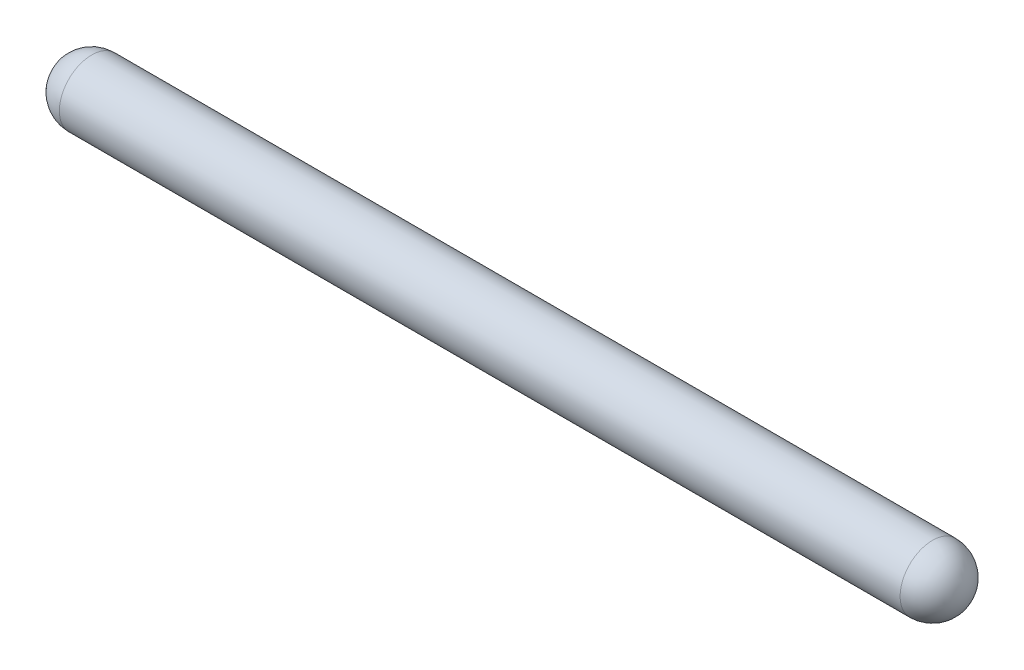
SolidWorks part; units mm, degrees
ref_plane "前基準面" through (0, 0, 0) normal (0, 0, 1) x (1, 0, 0)
ref_plane "上基準面" through (0, 0, 0) normal (0, 1, 0) x (1, 0, 0)
ref_plane "右基準面" through (0, 0, 0) normal (1, 0, 0) x (0, 0, -1)
sketch "草圖2" plane through (0, 0, 0) normal (0, 0, 1) x (1, 0, 0)
  line L1 (-29, 0) -> (36, 0)
  line L2 (-29, 0) -> (-29, 2.5)
  line L3 (-29, 2.5) -> (36, 2.5)
  line L4 (36, 0) -> (36, 2.5)
  point P4 (36, 1.25)
  dimension "D1" = 65
  dimension "D2" = 29
  dimension "D3" = 0
  dimension "D4" = 2.5
revolve "旋轉2" add sketch "草圖2" angle 360 about L1
dome "圓頂3" faces to dome 1 distance 2.5 reverse direction no elliptical dome no face at (36, 0, 2.5) parameters "D1"=2.5
dome "圓頂4" faces to dome 1 distance 2.5 reverse direction no elliptical dome no face at (-29, 0, 2.5) parameters "D1"=2.5
